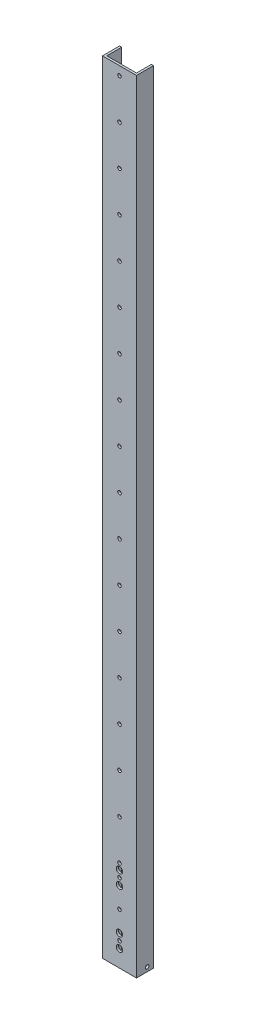
SolidWorks part; units mm, degrees
ref_plane "Front" through (0, 0, 0) normal (0, 0, 1) x (1, 0, 0)
ref_plane "Top" through (0, 0, 0) normal (0, 1, 0) x (1, 0, 0)
ref_plane "Right" through (0, 0, 0) normal (1, 0, 0) x (0, 0, -1)
sketch "Sketch1" plane through (0, 0, 0) normal (0, 1, 0) x (1, 0, 0)
  line L0 (3.175, 3.175) -> (3.175, 25.4)
  line L1 (0, 0) -> (50.8, 0)
  line L2 (0, 0) -> (0, 25.4)
  line L4 (50.8, 0) -> (50.8, 25.4)
  line L5 (3.175, 3.175) -> (47.625, 3.175)
  line L6 (47.625, 3.175) -> (47.625, 25.4)
  line L7 (0, 25.4) -> (3.175, 25.4)
  line L8 (50.8, 25.4) -> (47.625, 25.4)
  dimension "D1" = 25.4
  dimension "D2" = 50.8
  dimension "D3" = 3.175
extrude "Boss-Extrude1" add sketch "Sketch1" along normal blind 1168.4
sketch "Sketch2" plane through (0, 0, 0) normal (0, 0, 1) x (1, 0, 0)
  line L0 (25.4, 0) -> (25.4, 76.2) construction
  line L1 (0, 0) -> (50.8, 0) construction
  circle A0 centre (25.4, 76.2) radius 2.667
  circle A1 centre (25.4, 136.144) radius 2.667
  circle A2 centre (25.4, 196.088) radius 2.667
  circle A3 centre (25.4, 256.032) radius 2.667
  circle A4 centre (25.4, 315.976) radius 2.667
  circle A5 centre (25.4, 375.92) radius 2.667
  circle A6 centre (25.4, 435.864) radius 2.667
  circle A7 centre (25.4, 495.808) radius 2.667
  circle A8 centre (25.4, 555.752) radius 2.667
  circle A11 centre (25.4, 615.696) radius 2.667
  circle A12 centre (25.4, 675.64) radius 2.667
  circle A13 centre (25.4, 735.584) radius 2.667
  circle A14 centre (25.4, 795.528) radius 2.667
  circle A15 centre (25.4, 855.472) radius 2.667
  circle A16 centre (25.4, 915.416) radius 2.667
  circle A17 centre (25.4, 975.36) radius 2.667
  circle A18 centre (25.4, 1035.304) radius 2.667
  circle A19 centre (25.4, 1095.248) radius 2.667
  circle A20 centre (25.4, 1155.192) radius 2.667
  dimension "D2" = 5.334
  dimension "D1" = 76.2
  dimension "D3" = 19
extrude "Igus_Holes" cut sketch "Sketch2" against normal up to next
sketch "Sketch3" plane through (0, 0, -3.175) normal (0, 0, -1) x (-1, 0, 0)
  line L0 (-25.4, 0) -> (-25.4, 25.4) construction
  line L1 (-47.625, 0) -> (-3.175, 0) construction
  circle A0 centre (-25.4, 25.4) radius 4.7625
  circle A8 centre (-25.4, 35.4) radius 2.667
  circle A9 centre (-25.4, 117) radius 2.667
  circle A10 centre (-25.4, 45.4) radius 4.7625 construction
  circle A11 centre (-25.4, 45.4) radius 4.7625
  circle A12 centre (-25.4, 107) radius 4.7625 construction
  circle A13 centre (-25.4, 107) radius 4.7625
  circle A14 centre (-25.4, 127) radius 4.7625 construction
  circle A15 centre (-25.4, 127) radius 4.7625
  dimension "D2" = 9.525
  dimension "D4" = 5.334
  dimension "D3" = 5.334
  dimension "D1" = 25.4
extrude "Cut-Extrude2" cut sketch "Sketch3" against normal up to next
sketch "Sketch4" plane through (0, 0, 0) normal (-1, 0, 0) x (0, 0, 1)
  line L0 (-15.875, 0) -> (-15.875, 6.35) construction
  line L2 (-25.4, 0) -> (0, 0) construction
  line L3 (-15.875, 6.35) -> (-25.4, 6.35) construction
  line L4 (-25.4, 1168.4) -> (-25.4, 0) construction
  circle A0 centre (-15.875, 6.35) radius 2.667
  dimension "D2" = 5.334
  dimension "D1" = 6.35
  dimension "D3" = 9.525
extrude "Cut-Extrude3" cut sketch "Sketch4" against normal through all
ref_plane "Mid_Plane" through (25.4, 0, 0) normal (1, 0, 0) x (0, 0, -1)
